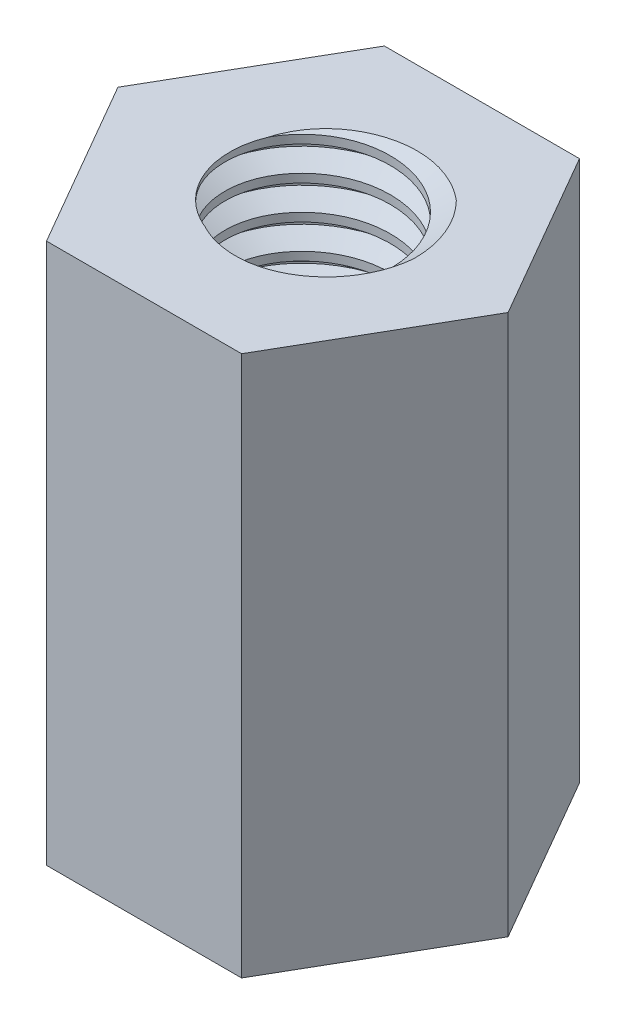
SolidWorks part; units mm, degrees
ref_plane "Front Plane" through (0, 0, 0) normal (0, 0, 1) x (1, 0, 0)
ref_plane "Top Plane" through (0, 0, 0) normal (0, 1, 0) x (1, 0, 0)
ref_plane "Right Plane" through (0, 0, 0) normal (1, 0, 0) x (0, 0, -1)
sketch "Sketch1" plane through (0, 0, 0) normal (0, 1, 0) x (1, 0, 0)
  line L1 (2.8868, 0) -> (1.4434, 2.5)
  line L2 (1.4434, 2.5) -> (-1.4434, 2.5)
  line L3 (-1.4434, 2.5) -> (-2.8868, 0)
  line L4 (-2.8868, 0) -> (-1.4434, -2.5)
  line L5 (-1.4434, -2.5) -> (1.4434, -2.5)
  line L6 (1.4434, -2.5) -> (2.8868, 0)
  circle A0 centre (0, 0) radius 2.5 construction
extrude "Boss-Extrude1" add sketch "Sketch1" along normal blind 8
sketch "Sketch2" plane through (0, 0, 0) normal (0, 1, 0) x (1, 0, 0)
  circle A0 centre (0, 0) radius 1.5
  point P3 (0, 0)
extrude "Cut-Extrude2" cut sketch "Sketch2" along normal blind 8
thread "Thread1" pitch 0.5 method extrude profile "Thread Profile3" start angle 0, offset 0, length 0, pitch 0.5, diameter 3
ref_plane "Plane3" through (1.5, 0, 0) normal (0, 0, 1) x (1, 0, 0)
sketch "Thread Profile3" plane through (1.5, 0, 0) normal (0, 0, 1) x (1, 0, 0)
  line L0 (0, 0) -> (0, 0.5) construction
  line L11 (0, 0) -> (0, 0.4375)
  line L12 (0, 0.4375) -> (-0.2706, 0.2812)
  line L13 (-0.2706, 0.2812) -> (-0.2706, 0.1562)
  line L15 (-0.2706, 0.1562) -> (0, 0)
  line L17 (-0.2706, 0.2187) -> (0, 0.2187) construction
  point P2 (0, 0)
  dimension "Pitch" = 0.5
  dimension "Profile_Angle" = 60
  dimension "Profile_Land" = 0.125
  dimension "Profile_Height" = 0.2706
ref_plane "Plane4" through (0, 8, 0) normal (0, 1, 0) x (1, 0, 0)
sketch "Sketch17" plane through (0, 8, 0) normal (0, 1, 0) x (1, 0, 0)
  line L1 (4.1869, 5.8423) -> (-5.6459, 5.8423)
  line L2 (4.1869, 5.8423) -> (4.1869, -6.0435)
  line L3 (4.1869, -6.0435) -> (-5.6459, -6.0435)
  line L4 (-5.6459, 5.8423) -> (-5.6459, -6.0435)
extrude "Cut-Extrude3" cut sketch "Sketch17" along normal blind 8
